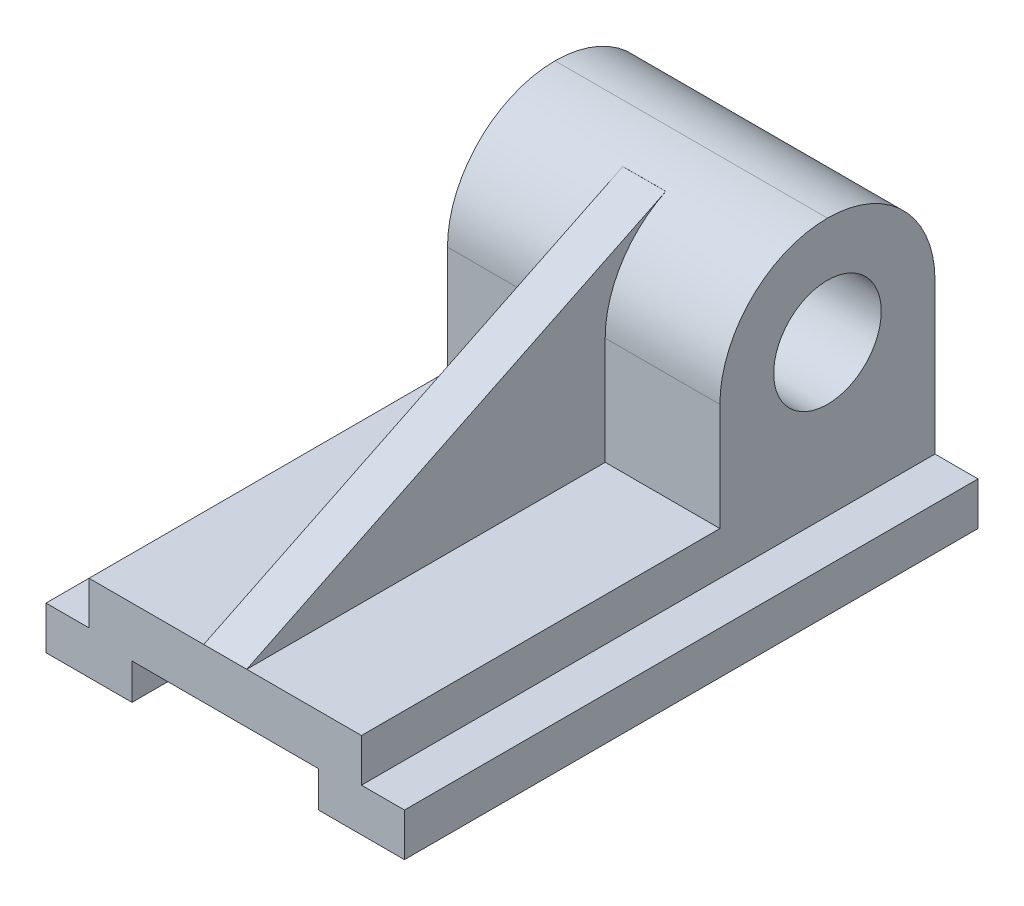
SolidWorks part; units mm, degrees
ref_plane "Front Plane" through (0, 0, 0) normal (0, 0, 1) x (1, 0, 0)
ref_plane "Top Plane" through (0, 0, 0) normal (0, 1, 0) x (1, 0, 0)
ref_plane "Right Plane" through (0, 0, 0) normal (1, 0, 0) x (0, 0, -1)
sketch "Sketch2" plane through (0, 0, 0) normal (0, 0, 1) x (1, 0, 0)
  line L0 (-96.52, 5.08) -> (-127, 5.08)
  line L1 (-127, 5.08) -> (-127, -25.4)
  line L2 (-127, -25.4) -> (-66.04, -25.4)
  line L3 (-66.04, -25.4) -> (-66.04, 0)
  line L4 (-66.04, 0) -> (66.04, 0)
  line L5 (66.04, 0) -> (66.04, -25.4)
  line L6 (66.04, -25.4) -> (127, -25.4)
  line L7 (127, -25.4) -> (127, 5.08)
  line L8 (127, 5.08) -> (96.52, 5.08)
  line L9 (96.52, 5.08) -> (96.52, 35.56)
  line L10 (96.52, 35.56) -> (-96.52, 35.56)
  line L11 (-96.52, 35.56) -> (-96.52, 5.08)
  point P3 (0, 0)
  point P14 (127, -10.16)
  point P15 (-111.76, 5.08)
  dimension "D1" = 132.08
  dimension "D2" = 254
  dimension "D3" = 30.48
  dimension "D4" = 25.4
  dimension "D5" = 60.96
  dimension "D6" = 30.48
  dimension "D7" = 30.48
  dimension "D8" = 193.04
  dimension "D9" = 25.4
extrude "Boss-Extrude1" add sketch "Sketch2" along normal blind 406.4
sketch "Sketch3" plane through (0, 35.56, 0) normal (0, 1, 0) x (1, 0, 0)
  line L0 (96.52, -406.4) -> (96.52, 0) construction
  line L1 (-96.52, 0) -> (96.52, 0)
  line L2 (-96.52, 0) -> (-96.52, -152.4)
  line L3 (-96.52, -152.4) -> (96.52, -152.4)
  line L4 (96.52, 0) -> (96.52, -152.4)
  dimension "D1" = 152.4
extrude "Boss-Extrude2" add sketch "Sketch3" along normal blind 152.4
sketch "Sketch4" plane through (0, 35.56, 0) normal (0, 1, 0) x (1, 0, 0)
  line L0 (0, -152.4) -> (0, -406.4) construction
  line L1 (-96.52, -152.4) -> (96.52, -152.4) construction
  line L2 (96.52, -406.4) -> (-96.52, -406.4) construction
  line L4 (-15.24, -406.4) -> (15.24, -406.4)
  line L5 (-15.24, -406.4) -> (-15.24, -152.4)
  line L6 (-15.24, -152.4) -> (15.24, -152.4)
  line L7 (15.24, -406.4) -> (15.24, -152.4)
  line L8 (-15.24, -406.4) -> (15.24, -152.4) construction
  line L9 (-15.24, -152.4) -> (15.24, -406.4) construction
  point P6 (0, -279.4)
  dimension "D1" = 30.48
extrude "Boss-Extrude3" add sketch "Sketch4" along normal blind 144.78
sketch "Sketch5" plane through (96.52, 0, 0) normal (1, 0, 0) x (0, 0, -1)
  line L0 (-76.2, 187.96) -> (-76.2, 5.08) construction
  line L1 (-152.4, 187.96) -> (0, 187.96) construction
  line L2 (-406.4, 5.08) -> (0, 5.08) construction
  circle A0 centre (-76.2, 111.76) radius 38.1
  dimension "D1" = 106.68
  dimension "D2" = 76.2
extrude "Cut-Extrude1" cut sketch "Sketch5" against normal blind 193.04
fillet "Fillet1" radius 76.2 2 edges at (0, 187.96, 152.4) (0, 187.96, 0)
chamfer "Chamfer2" distance 144.78 distance2 296.926 1 edges at (0, 180.34, 406.4) first distance on face at (0, 26.3525, 406.4)
equation "\"ChamferHeightIn\"= 13.0 * sin ( \"ChamferAngleDeg\" )"
equation "\"ChamferAngleDeg\"= 2 * atn ( 3 / 13 )"
equation "\"ChamferDistanceIn\"= sqr ( 13 ^ 2 - \"ChamferHeightIn\" ^ 2 )"
